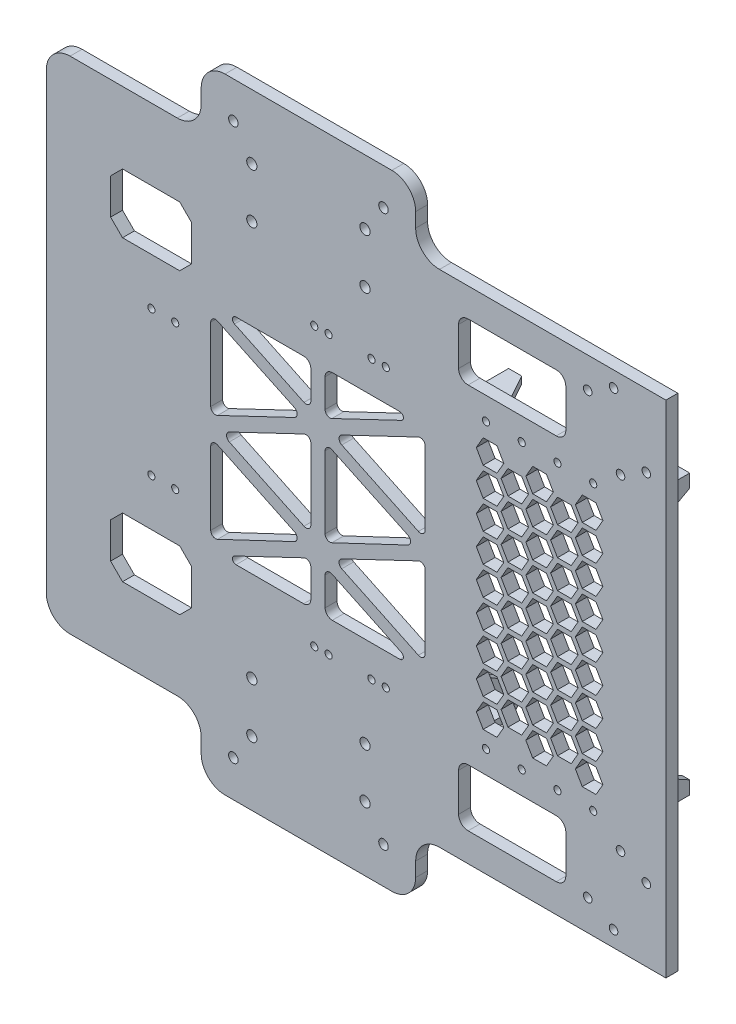
SolidWorks part; units mm, degrees
ref_plane "前视基准面" through (0, 0, 0) normal (0, 0, 1) x (1, 0, 0)
ref_plane "上视基准面" through (0, 0, 0) normal (0, 1, 0) x (1, 0, 0)
ref_plane "右视基准面" through (0, 0, 0) normal (1, 0, 0) x (0, 0, -1)
sketch "草图1" plane through (0, 0, 0) normal (0, 0, 1) x (1, 0, 0)
  line L2 (-130, 95) -> (-130, -95)
  line L3 (-120, -105) -> (-75, -105)
  line L4 (130, 95) -> (130, -95)
  line L5 (126.7518, 102.3765) -> (130, 105) construction
  line L6 (-130, -105) -> (-126.7518, -102.3765) construction
  line L9 (-65, -115) -> (-65, -121)
  line L10 (-55, -131) -> (15, -131)
  line L11 (25, -121) -> (25, -115)
  line L13 (35, -105) -> (120, -105)
  line L14 (126.7518, -102.3765) -> (130, -105) construction
  line L15 (-130, 105) -> (-126.7518, 102.3765) construction
  line L16 (-130, 0) -> (130, 0) construction
  line L17 (35, 105) -> (120, 105)
  line L18 (25, 121) -> (25, 115)
  line L19 (-55, 131) -> (15, 131)
  line L20 (-65, 115) -> (-65, 121)
  line L21 (-120, 105) -> (-75, 105)
  arc A1 (-120, -105) -> (-130, -95) centre (-120, -95) cw
  arc A3 (120, -105) -> (130, -95) centre (120, -95) ccw
  arc A8 (-65, -115) -> (-75, -105) centre (-75, -115) ccw
  arc A9 (25, -115) -> (35, -105) centre (35, -115) cw
  arc A10 (-55, -131) -> (-65, -121) centre (-55, -121) cw
  arc A11 (15, -131) -> (25, -121) centre (15, -121) ccw
  arc A12 (15, 131) -> (25, 121) centre (15, 121) cw
  arc A13 (-55, 131) -> (-65, 121) centre (-55, 121) ccw
  arc A14 (25, 115) -> (35, 105) centre (35, 115) ccw
  arc A15 (-65, 115) -> (-75, 105) centre (-75, 115) cw
  arc A16 (120, 105) -> (130, 95) centre (120, 95) cw
  arc A17 (-120, 105) -> (-130, 95) centre (-120, 95) ccw
  point P0 (0, 0)
  point P40 (25, -105)
  point P45 (25, 105)
  dimension "D2" = 10
  dimension "D3" = 65
  dimension "D4" = 10
  dimension "D5" = 105
  dimension "D7" = 10
  dimension "D8" = 10
  dimension "D10" = 10
  dimension "D12" = 10
  dimension "D13" = 105
  dimension "D18" = 90
  dimension "D19" = 6
extrude "凸台-拉伸1" add sketch "草图1" along normal blind 5
sketch "草图4" plane through (0, 0, 0) normal (0, 0, -1) x (-1, 0, 0)
  line L0 (-39, -47.5) -> (-39, -58.5)
  line L1 (-39, -58.5) -> (-50, -58.5)
  line L2 (-50, -58.5) -> (-50, -55.5)
  line L3 (-50, -55.5) -> (-42, -55.5)
  line L4 (-42, -55.5) -> (-42, -47.5)
  line L5 (-42, -47.5) -> (-39, -47.5)
  line L6 (-130, 0) -> (-25.5592, 0) construction
  line L7 (-130, -95) -> (-130, 95) construction
  line L10 (-130, -95) -> (-130, 95) construction
  dimension "D1" = 11
  dimension "D2" = 11
  dimension "D3" = 3
  dimension "D4" = 3
  dimension "D5" = 80
  dimension "D7" = 55.5
extrude "凸台-拉伸2" add sketch "草图4" along normal blind 20
sketch "草图5" plane through (0, -58.5, 0) normal (0, -1, 0) x (1, 0, 0)
  line L0 (50, -10) -> (44.5, -20)
  line L1 (50, -20) -> (50, 0) construction
  line L2 (50, -20) -> (39, -20) construction
  line L3 (44.5, -20) -> (50, -20)
  line L4 (50, -20) -> (50, -10)
  dimension "D1" = 10
  dimension "D2" = 5.5
extrude "切除-拉伸3" cut sketch "草图5" against normal blind 10
sketch "草图6" plane through (39, 0, 0) normal (-1, 0, 0) x (0, 0, 1)
  line L0 (-20, -53) -> (-10, -47.5)
  line L1 (-20, -58.5) -> (-20, -47.5) construction
  line L2 (-20, -47.5) -> (0, -47.5) construction
  line L3 (-10, -47.5) -> (-20, -47.5)
  line L4 (-20, -47.5) -> (-20, -53)
  dimension "D1" = 10
  dimension "D2" = 5.5
extrude "切除-拉伸4" cut sketch "草图6" against normal blind 10
ref_plane "基准面2" through (77, 0, 0) normal (1, 0, 0) x (0, 0, -1)
mirror "镜向1" about plane through (77, 0, 0) normal (1, 0, 0) of "凸台-拉伸2", "切除-拉伸4", "切除-拉伸3"
mirror "镜向2" about plane through (0, 0, 0) normal (0, 1, 0) of "镜向1"
sketch "草图7" plane through (0, 0, 0) normal (0, 0, -1) x (-1, 0, 0)
  line L4 (-112, -55.5) -> (-104, -55.5) construction
  line L5 (-112, 47.5) -> (-112, 55.5) construction
  line L6 (-112, 55.5) -> (-104, 55.5) construction
  line L7 (-92.013, 36) -> (-94.8997, 41)
  line L8 (-94.8997, 41) -> (-100.6732, 41)
  line L9 (-100.6732, 41) -> (-103.56, 36)
  line L10 (-103.56, 36) -> (-100.6732, 31)
  line L11 (-100.6732, 31) -> (-94.8997, 31)
  line L12 (-94.8997, 31) -> (-92.013, 36)
  line L13 (-77.0019, 36) -> (-97.7865, 36) construction
  line L14 (-74.1151, 31) -> (-71.2284, 36)
  line L15 (-71.2284, 36) -> (-74.1151, 41)
  line L16 (-74.1151, 41) -> (-79.8886, 41)
  line L17 (-79.8886, 41) -> (-82.7754, 36)
  line L18 (-82.7754, 36) -> (-79.8886, 31)
  line L19 (-79.8886, 31) -> (-74.1151, 31)
  line L20 (-92.013, 24) -> (-94.8997, 29)
  line L21 (-93.1677, 30) -> (-90.2809, 25)
  line L22 (-90.2809, 25) -> (-84.5074, 25)
  line L23 (-84.5074, 25) -> (-81.6207, 30)
  line L24 (-81.6207, 30) -> (-84.5074, 35)
  line L25 (-84.5074, 35) -> (-90.2809, 35)
  line L26 (-90.2809, 35) -> (-93.1677, 30)
  line L27 (-84.5074, 37) -> (-81.6207, 42)
  line L28 (-81.6207, 42) -> (-84.5074, 47)
  line L29 (-84.5074, 47) -> (-90.2809, 47)
  line L30 (-90.2809, 47) -> (-93.1677, 42)
  line L31 (-93.1677, 42) -> (-90.2809, 37)
  line L32 (-90.2809, 37) -> (-84.5074, 37)
  line L33 (-79.8886, 43) -> (-74.1151, 43)
  line L34 (-74.1151, 43) -> (-71.2284, 48)
  line L35 (-71.2284, 48) -> (-74.1151, 53)
  line L36 (-74.1151, 53) -> (-79.8886, 53)
  line L37 (-79.8886, 53) -> (-82.7754, 48)
  line L38 (-82.7754, 48) -> (-79.8886, 43)
  line L39 (-94.8997, 43) -> (-92.013, 48)
  line L40 (-92.013, 48) -> (-94.8997, 53)
  line L41 (-94.8997, 53) -> (-100.6732, 53)
  line L42 (-100.6732, 53) -> (-103.56, 48)
  line L43 (-103.56, 48) -> (-100.6732, 43)
  line L44 (-100.6732, 43) -> (-94.8997, 43)
  line L45 (-72.3831, 42) -> (-69.4963, 37)
  line L46 (-69.4963, 37) -> (-63.7228, 37)
  line L47 (-63.7228, 37) -> (-60.8361, 42)
  line L48 (-60.8361, 42) -> (-63.7228, 47)
  line L49 (-63.7228, 47) -> (-69.4963, 47)
  line L50 (-69.4963, 47) -> (-72.3831, 42)
  line L51 (-94.8997, 29) -> (-100.6732, 29)
  line L52 (-100.6732, 29) -> (-103.56, 24)
  line L53 (-103.56, 24) -> (-100.6732, 19)
  line L54 (-100.6732, 19) -> (-94.8997, 19)
  line L55 (-94.8997, 19) -> (-92.013, 24)
  line L56 (-93.1677, 18) -> (-90.2809, 13)
  line L57 (-90.2809, 13) -> (-84.5074, 13)
  line L58 (-84.5074, 13) -> (-81.6207, 18)
  line L59 (-81.6207, 18) -> (-84.5074, 23)
  line L60 (-84.5074, 23) -> (-90.2809, 23)
  line L61 (-90.2809, 23) -> (-93.1677, 18)
  line L62 (-74.1151, 19) -> (-71.2284, 24)
  line L63 (-71.2284, 24) -> (-74.1151, 29)
  line L64 (-74.1151, 29) -> (-79.8886, 29)
  line L65 (-79.8886, 29) -> (-82.7754, 24)
  line L66 (-82.7754, 24) -> (-79.8886, 19)
  line L67 (-79.8886, 19) -> (-74.1151, 19)
  line L68 (-72.3831, 30) -> (-69.4963, 25)
  line L69 (-69.4963, 25) -> (-63.7228, 25)
  line L70 (-63.7228, 25) -> (-60.8361, 30)
  line L71 (-60.8361, 30) -> (-63.7228, 35)
  line L72 (-63.7228, 35) -> (-69.4963, 35)
  line L73 (-69.4963, 35) -> (-72.3831, 30)
  line L74 (-92.013, 12) -> (-94.8997, 17)
  line L75 (-94.8997, 17) -> (-100.6732, 17)
  line L76 (-100.6732, 17) -> (-103.56, 12)
  line L77 (-103.56, 12) -> (-100.6732, 7)
  line L78 (-100.6732, 7) -> (-94.8997, 7)
  line L79 (-94.8997, 7) -> (-92.013, 12)
  line L80 (-93.1677, 6) -> (-90.2809, 1)
  line L81 (-90.2809, 1) -> (-84.5074, 1)
  line L82 (-84.5074, 1) -> (-81.6207, 6)
  line L83 (-81.6207, 6) -> (-84.5074, 11)
  line L84 (-84.5074, 11) -> (-90.2809, 11)
  line L85 (-90.2809, 11) -> (-93.1677, 6)
  line L86 (-74.1151, 7) -> (-71.2284, 12)
  line L87 (-71.2284, 12) -> (-74.1151, 17)
  line L88 (-74.1151, 17) -> (-79.8886, 17)
  line L89 (-79.8886, 17) -> (-82.7754, 12)
  line L90 (-82.7754, 12) -> (-79.8886, 7)
  line L91 (-79.8886, 7) -> (-74.1151, 7)
  line L92 (-72.3831, 18) -> (-69.4963, 13)
  line L93 (-69.4963, 13) -> (-63.7228, 13)
  line L94 (-63.7228, 13) -> (-60.8361, 18)
  line L95 (-60.8361, 18) -> (-63.7228, 23)
  line L96 (-63.7228, 23) -> (-69.4963, 23)
  line L97 (-69.4963, 23) -> (-72.3831, 18)
  line L98 (-92.013, 0) -> (-94.8997, 5)
  line L99 (-94.8997, 5) -> (-100.6732, 5)
  line L100 (-100.6732, 5) -> (-103.56, 0)
  line L101 (-103.56, 0) -> (-100.6732, -5)
  line L102 (-100.6732, -5) -> (-94.8997, -5)
  line L103 (-94.8997, -5) -> (-92.013, 0)
  line L104 (-93.1677, -6) -> (-90.2809, -11)
  line L105 (-90.2809, -11) -> (-84.5074, -11)
  line L106 (-84.5074, -11) -> (-81.6207, -6)
  line L107 (-81.6207, -6) -> (-84.5074, -1)
  line L108 (-84.5074, -1) -> (-90.2809, -1)
  line L109 (-90.2809, -1) -> (-93.1677, -6)
  line L110 (-74.1151, -5) -> (-71.2284, 0)
  line L111 (-71.2284, 0) -> (-74.1151, 5)
  line L112 (-74.1151, 5) -> (-79.8886, 5)
  line L113 (-79.8886, 5) -> (-82.7754, 0)
  line L114 (-82.7754, 0) -> (-79.8886, -5)
  line L115 (-79.8886, -5) -> (-74.1151, -5)
  line L116 (-72.3831, 6) -> (-69.4963, 1)
  line L117 (-69.4963, 1) -> (-63.7228, 1)
  line L118 (-63.7228, 1) -> (-60.8361, 6)
  line L119 (-60.8361, 6) -> (-63.7228, 11)
  line L120 (-63.7228, 11) -> (-69.4963, 11)
  line L121 (-69.4963, 11) -> (-72.3831, 6)
  line L122 (-92.013, -12) -> (-94.8997, -7)
  line L123 (-94.8997, -7) -> (-100.6732, -7)
  line L124 (-100.6732, -7) -> (-103.56, -12)
  line L125 (-103.56, -12) -> (-100.6732, -17)
  line L126 (-100.6732, -17) -> (-94.8997, -17)
  line L127 (-94.8997, -17) -> (-92.013, -12)
  line L128 (-93.1677, -18) -> (-90.2809, -23)
  line L129 (-90.2809, -23) -> (-84.5074, -23)
  line L130 (-84.5074, -23) -> (-81.6207, -18)
  line L131 (-81.6207, -18) -> (-84.5074, -13)
  line L132 (-84.5074, -13) -> (-90.2809, -13)
  line L133 (-90.2809, -13) -> (-93.1677, -18)
  line L134 (-74.1151, -17) -> (-71.2284, -12)
  line L135 (-71.2284, -12) -> (-74.1151, -7)
  line L136 (-74.1151, -7) -> (-79.8886, -7)
  line L137 (-79.8886, -7) -> (-82.7754, -12)
  line L138 (-82.7754, -12) -> (-79.8886, -17)
  line L139 (-79.8886, -17) -> (-74.1151, -17)
  line L140 (-72.3831, -6) -> (-69.4963, -11)
  line L141 (-69.4963, -11) -> (-63.7228, -11)
  line L142 (-63.7228, -11) -> (-60.8361, -6)
  line L143 (-60.8361, -6) -> (-63.7228, -1)
  line L144 (-63.7228, -1) -> (-69.4963, -1)
  line L145 (-69.4963, -1) -> (-72.3831, -6)
  line L146 (-92.013, -24) -> (-94.8997, -19)
  line L147 (-94.8997, -19) -> (-100.6732, -19)
  line L148 (-100.6732, -19) -> (-103.56, -24)
  line L149 (-103.56, -24) -> (-100.6732, -29)
  line L150 (-100.6732, -29) -> (-94.8997, -29)
  line L151 (-94.8997, -29) -> (-92.013, -24)
  line L152 (-93.1677, -30) -> (-90.2809, -35)
  line L153 (-90.2809, -35) -> (-84.5074, -35)
  line L154 (-84.5074, -35) -> (-81.6207, -30)
  line L155 (-81.6207, -30) -> (-84.5074, -25)
  line L156 (-84.5074, -25) -> (-90.2809, -25)
  line L157 (-90.2809, -25) -> (-93.1677, -30)
  line L158 (-74.1151, -29) -> (-71.2284, -24)
  line L159 (-71.2284, -24) -> (-74.1151, -19)
  line L160 (-74.1151, -19) -> (-79.8886, -19)
  line L161 (-79.8886, -19) -> (-82.7754, -24)
  line L162 (-82.7754, -24) -> (-79.8886, -29)
  line L163 (-79.8886, -29) -> (-74.1151, -29)
  line L164 (-72.3831, -18) -> (-69.4963, -23)
  line L165 (-69.4963, -23) -> (-63.7228, -23)
  line L166 (-63.7228, -23) -> (-60.8361, -18)
  line L167 (-60.8361, -18) -> (-63.7228, -13)
  line L168 (-63.7228, -13) -> (-69.4963, -13)
  line L169 (-69.4963, -13) -> (-72.3831, -18)
  line L170 (-92.013, -36) -> (-94.8997, -31)
  line L171 (-94.8997, -31) -> (-100.6732, -31)
  line L172 (-100.6732, -31) -> (-103.56, -36)
  line L173 (-103.56, -36) -> (-100.6732, -41)
  line L174 (-100.6732, -41) -> (-94.8997, -41)
  line L175 (-94.8997, -41) -> (-92.013, -36)
  line L176 (-93.1677, -42) -> (-90.2809, -47)
  line L177 (-90.2809, -47) -> (-84.5074, -47)
  line L178 (-84.5074, -47) -> (-81.6207, -42)
  line L179 (-81.6207, -42) -> (-84.5074, -37)
  line L180 (-84.5074, -37) -> (-90.2809, -37)
  line L181 (-90.2809, -37) -> (-93.1677, -42)
  line L182 (-74.1151, -41) -> (-71.2284, -36)
  line L183 (-71.2284, -36) -> (-74.1151, -31)
  line L184 (-74.1151, -31) -> (-79.8886, -31)
  line L185 (-79.8886, -31) -> (-82.7754, -36)
  line L186 (-82.7754, -36) -> (-79.8886, -41)
  line L187 (-79.8886, -41) -> (-74.1151, -41)
  line L188 (-72.3831, -30) -> (-69.4963, -35)
  line L189 (-69.4963, -35) -> (-63.7228, -35)
  line L190 (-63.7228, -35) -> (-60.8361, -30)
  line L191 (-60.8361, -30) -> (-63.7228, -25)
  line L192 (-63.7228, -25) -> (-69.4963, -25)
  line L193 (-69.4963, -25) -> (-72.3831, -30)
  line L194 (-92.013, -48) -> (-94.8997, -43)
  line L195 (-94.8997, -43) -> (-100.6732, -43)
  line L196 (-100.6732, -43) -> (-103.56, -48)
  line L197 (-103.56, -48) -> (-100.6732, -53)
  line L198 (-100.6732, -53) -> (-94.8997, -53)
  line L199 (-94.8997, -53) -> (-92.013, -48)
  line L206 (-74.1151, -53) -> (-71.2284, -48)
  line L207 (-71.2284, -48) -> (-74.1151, -43)
  line L208 (-74.1151, -43) -> (-79.8886, -43)
  line L209 (-79.8886, -43) -> (-82.7754, -48)
  line L210 (-82.7754, -48) -> (-79.8886, -53)
  line L211 (-79.8886, -53) -> (-74.1151, -53)
  line L212 (-72.3831, -42) -> (-69.4963, -47)
  line L213 (-69.4963, -47) -> (-63.7228, -47)
  line L214 (-63.7228, -47) -> (-60.8361, -42)
  line L215 (-60.8361, -42) -> (-63.7228, -37)
  line L216 (-63.7228, -37) -> (-69.4963, -37)
  line L217 (-69.4963, -37) -> (-72.3831, -42)
  line L218 (-61.9908, 36) -> (-59.104, 31)
  line L219 (-61.9908, 48) -> (-59.104, 43)
  line L220 (-59.104, 43) -> (-53.3305, 43)
  line L221 (-53.3305, 43) -> (-50.4438, 48)
  line L222 (-50.4438, 48) -> (-53.3305, 53)
  line L223 (-53.3305, 53) -> (-59.104, 53)
  line L224 (-59.104, 53) -> (-61.9908, 48)
  line L225 (-59.104, 31) -> (-53.3305, 31)
  line L226 (-53.3305, 31) -> (-50.4438, 36)
  line L227 (-50.4438, 36) -> (-53.3305, 41)
  line L228 (-53.3305, 41) -> (-59.104, 41)
  line L229 (-59.104, 41) -> (-61.9908, 36)
  line L230 (-61.9908, 24) -> (-59.104, 19)
  line L231 (-59.104, 19) -> (-53.3305, 19)
  line L232 (-53.3305, 19) -> (-50.4438, 24)
  line L233 (-50.4438, 24) -> (-53.3305, 29)
  line L234 (-53.3305, 29) -> (-59.104, 29)
  line L235 (-59.104, 29) -> (-61.9908, 24)
  line L236 (-61.9908, 12) -> (-59.104, 7)
  line L237 (-59.104, 7) -> (-53.3305, 7)
  line L238 (-53.3305, 7) -> (-50.4438, 12)
  line L239 (-50.4438, 12) -> (-53.3305, 17)
  line L240 (-53.3305, 17) -> (-59.104, 17)
  line L241 (-59.104, 17) -> (-61.9908, 12)
  line L242 (-61.9908, 0) -> (-59.104, -5)
  line L243 (-59.104, -5) -> (-53.3305, -5)
  line L244 (-53.3305, -5) -> (-50.4438, 0)
  line L245 (-50.4438, 0) -> (-53.3305, 5)
  line L246 (-53.3305, 5) -> (-59.104, 5)
  line L247 (-59.104, 5) -> (-61.9908, 0)
  line L248 (-61.9908, -12) -> (-59.104, -17)
  line L249 (-59.104, -17) -> (-53.3305, -17)
  line L250 (-53.3305, -17) -> (-50.4438, -12)
  line L251 (-50.4438, -12) -> (-53.3305, -7)
  line L252 (-53.3305, -7) -> (-59.104, -7)
  line L253 (-59.104, -7) -> (-61.9908, -12)
  line L254 (-61.9908, -24) -> (-59.104, -29)
  line L255 (-59.104, -29) -> (-53.3305, -29)
  line L256 (-53.3305, -29) -> (-50.4438, -24)
  line L257 (-50.4438, -24) -> (-53.3305, -19)
  line L258 (-53.3305, -19) -> (-59.104, -19)
  line L259 (-59.104, -19) -> (-61.9908, -24)
  line L260 (-61.9908, -36) -> (-59.104, -41)
  line L261 (-59.104, -41) -> (-53.3305, -41)
  line L262 (-53.3305, -41) -> (-50.4438, -36)
  line L263 (-50.4438, -36) -> (-53.3305, -31)
  line L264 (-53.3305, -31) -> (-59.104, -31)
  line L265 (-59.104, -31) -> (-61.9908, -36)
  line L266 (-61.9908, -48) -> (-59.104, -53)
  line L267 (-59.104, -53) -> (-53.3305, -53)
  line L268 (-53.3305, -53) -> (-50.4438, -48)
  line L269 (-50.4438, -48) -> (-53.3305, -43)
  line L270 (-53.3305, -43) -> (-59.104, -43)
  line L271 (-59.104, -43) -> (-61.9908, -48)
  line L272 (-93.1677, -54) -> (-90.2809, -59) [skipped]
  line L273 (-90.2809, -59) -> (-84.5074, -59) [skipped]
  line L274 (-84.5074, -59) -> (-81.6207, -54) [skipped]
  line L275 (-81.6207, -54) -> (-84.5074, -49) [skipped]
  line L276 (-84.5074, -49) -> (-90.2809, -49) [skipped]
  line L277 (-90.2809, -49) -> (-93.1677, -54) [skipped]
  circle A0 centre (-97.7865, 36) radius 5 construction
  circle A1 centre (-77.0019, 36) radius 5 construction
  circle A2 centre (-87.3942, 30) radius 5 construction
  circle A3 centre (-87.3942, 42) radius 5 construction
  circle A4 centre (-77.0019, 48) radius 5 construction
  circle A5 centre (-97.7865, 48) radius 5 construction
  circle A6 centre (-66.6096, 42) radius 5 construction
  circle A7 centre (-56.2173, 48) radius 5 construction
  point P4 (-87.3942, 37)
  dimension "D1" = 2
  dimension "D3" = 10
  dimension "D4" = 10
  dimension "D5" = 2
  dimension "D7" = 10
  dimension "D11" = 10
  dimension "D14" = 10
  dimension "D15" = 10
  dimension "D20" = 10
  dimension "D2" = 2
  dimension "D6" = 2
  dimension "D8" = 2
  dimension "D9" = 2
  dimension "D10" = 2
  dimension "D12" = 2
  dimension "D13" = 2
  dimension "D16" = 2
  dimension "D17" = 2
  dimension "D19" = 2
  dimension "D21" = 9
  dimension "D22" = 2.5
  dimension "D23" = 2.5
  dimension "D24" = 8.44
  dimension "D18" = 8
extrude "切除-拉伸5" cut sketch "草图7" against normal blind 5
sketch "草图8" plane through (0, 0, 0) normal (0, 0, -1) x (-1, 0, 0)
  line L0 (-75.3677, 120) -> (-75.3677, -120)
  line L1 (-100.0285, 77.2863) -> (-100.0285, -77.2863)
  line L2 (-100.0285, 77.2863) -> (-75.3677, 120)
  line L3 (-100.0285, -77.2863) -> (-75.3677, -120)
  line L4 (-37.1297, 0) -> (-146.8562, 0) construction
  dimension "D1" = 30
  dimension "D2" = 30
  dimension "D3" = 120
  dimension "D4" = 120
sketch "草图9" plane through (0, 0, 0) normal (0, 0, -1) x (-1, 0, 0)
  line L0 (148.8518, 0) -> (-37.1297, 0) construction
  line L1 (-29, 41) -> (-29, 4)
  line L2 (-25, -45) -> (13, -45)
  line L3 (61, -41) -> (61, -4)
  line L4 (57, 45) -> (19, 45)
  line L14 (-29, 41) -> (9.8049, 22.5)
  line L15 (57, 0) -> (19, -18.1163)
  line L16 (130, 95) -> (130, -95) construction
  line L17 (63, 93) -> (118, 93)
  line L18 (63, 93) -> (63, 66)
  line L19 (63, 66) -> (118, 66)
  line L20 (118, 93) -> (118, 66)
  line L21 (75, 105) -> (120, 105) construction
  line L22 (63, -66) -> (118, -66)
  line L23 (118, -93) -> (118, -66)
  line L24 (63, -93) -> (118, -93)
  line L25 (63, -93) -> (63, -66)
  line L26 (-120, 105) -> (-35, 105) construction
  line L27 (-43, 93) -> (-88, 93)
  line L28 (-43, 93) -> (-43, 69)
  line L29 (-43, 69) -> (-88, 69)
  line L30 (-88, 93) -> (-88, 69)
  line L31 (-130, -95) -> (-130, 95) construction
  line L32 (-43, -69) -> (-88, -69)
  line L33 (-88, -93) -> (-88, -69)
  line L34 (-43, -93) -> (-88, -93)
  line L35 (-43, -93) -> (-43, -69)
  line L36 (-25, 45) -> (13, 26.8837)
  line L37 (-25, -45) -> (13, -26.8837)
  line L38 (61, 41) -> (22.0746, 22.5575)
  line L39 (-25.5359, 0) -> (13, -18.258)
  line L40 (57, 45) -> (19, 26.8837)
  line L41 (57, -45) -> (19, -26.8837)
  line L42 (16, 61.4977) -> (16, -60.5731) construction
  line L43 (13, 45) -> (13, 26.8837)
  line L44 (19, 45) -> (19, 26.8837)
  line L45 (13, 18.258) -> (13, -18.258)
  line L46 (9.8049, 22.5) -> (-29, 4)
  line L47 (19, 18.1163) -> (57, 0)
  line L48 (22.0746, 22.5575) -> (61, 4)
  line L49 (13, 18.258) -> (-25.5359, 0)
  line L50 (19, 18.1163) -> (19, -18.1163)
  line L51 (22.0746, -22.5575) -> (61, -41)
  line L52 (9.8049, -22.5) -> (-29, -41)
  line L53 (9.8049, -22.5) -> (-29, -4)
  line L54 (22.0746, -22.5575) -> (61, -4)
  line L55 (13, -26.8837) -> (13, -45)
  line L56 (19, -26.8837) -> (19, -45)
  line L57 (13, 45) -> (-25, 45)
  line L58 (-29, -4) -> (-29, -41)
  line L59 (19, -45) -> (57, -45)
  line L60 (61, 4) -> (61, 41)
  line L61 (-44, 41) -> (-44, -37.8122) construction
  dimension "D1" = 45
  dimension "D2" = 45
  dimension "D3" = 15
  dimension "D4" = 90
  dimension "D5" = 1
  dimension "D7" = 12
  dimension "D8" = 12
  dimension "D9" = 27
  dimension "D10" = 55
  dimension "D11" = 12
  dimension "D12" = 45
  dimension "D13" = 42
  dimension "D14" = 24
  dimension "D21" = 4
  dimension "D22" = 4
  dimension "D23" = 4
  dimension "D24" = 4
  dimension "D26" = 4
  dimension "D27" = 3
  dimension "D28" = 45
extrude "切除-拉伸6" cut sketch "草图9" against normal blind 5 contours L27 L30 L29 L28 | L34 L35 L32 L33 | L4 L44 L40 | L48 L60 L38 | L47 L50 L15 | L54 L51 L3 | L56 L59 L41 | L55 L37 L2 | L53 L58 L52 | L45 L49 L39 | L46 L14 L1 | L43 L57 L36 | L57 L36 L43 region at (16.065, 22.5, 0) region at (-0.3333, -38.9612, 0) region at (-48.0249, -22.5192, 0) region at (-31.6667, 38.9612, 0) region at (-31.6667, 0, 0) region at (65.5, 81, 0) region at (65.5, -81, 0) region at (-0.3333, 38.9612, 0) region at (-48.0249, 22.5192, 0) region at (-0.1547, 0, 0) region at (-31.6667, -38.9612, 0) region at (16.065, -22.5, 0)
fillet "圆角1" radius 4 8 edges at (43, -93, 2.5) (88, -69, 2.5) (43, -69, 2.5) (88, -93, 2.5) (88, 69, 2.5) (43, 69, 2.5) (43, 93, 2.5) (88, 93, 2.5)
fillet "圆角2" radius 1.5 4 edges at (25, -45, 2.5) (-57, -45, 2.5) (25, 45, 2.5) (-57, 45, 2.5)
fillet "圆角3" radius 2 22 edges at (29, -4, 2.5) (29, 4, 2.5) (-13, -18.258, 2.5) (-61, -41, 2.5) (-61, 4, 2.5) (-13, -26.8837, 2.5) (-13, 18.258, 2.5) (-61, -4, 2.5) (-22.0746, -22.5575, 2.5) (25.5359, 0, 2.5) (-22.0746, 22.5575, 2.5) (-61, 41, 2.5) (-19, 26.8837, 2.5) (-19, -26.8837, 2.5) (-19, -18.1163, 2.5) (29, -41, 2.5) (29, 41, 2.5) (-57, 0, 2.5) (-9.8049, -22.5, 2.5) (-13, 26.8837, 2.5) (-9.8049, 22.5, 2.5) (-19, 18.1163, 2.5)
fillet "圆角4" radius 3 4 edges at (-13, -45, 2.5) (-13, 45, 2.5) (-19, -45, 2.5) (-19, 45, 2.5)
sketch "草图12" plane through (0, 0, 0) normal (0, 0, -1) x (-1, 0, 0)
  line L1 (-120, 105) -> (-130, 105)
  line L2 (-120, 105) -> (-120, -105)
  line L3 (-120, -105) -> (-130, -105)
  line L4 (-130, 105) -> (-130, -105)
extrude "凸台-拉伸3" add sketch "草图12" against normal up to surface (5 mm away) up to face at (65.5, 81, 5)
sketch "草图10" plane through (0, 0, 0) normal (0, 0, -1) x (-1, 0, 0)
  line L0 (-37.1297, 0) -> (-146.8562, 0) construction
  line L1 (-37.1297, 0) -> (-146.8562, 0) construction
  circle A0 centre (-121.782, 74.6081) radius 1.8 construction
  circle A1 centre (-110.9567, 68.3581) radius 1.8 construction
  circle A2 centre (-108.032, 98.4238) radius 1.8 construction
  circle A3 centre (-97.2067, 92.1738) radius 1.8 construction
  circle A4 centre (-3.75, 104) radius 2.15 construction
  circle A5 centre (-3.75, 104) radius 2.15
  circle A6 centre (-3.75, -104) radius 2.15
  circle A15 centre (-121.782, 74.6081) radius 1.8
  circle A16 centre (-110.9567, 68.3581) radius 1.8
  circle A17 centre (-108.032, 98.4238) radius 1.8
  circle A18 centre (-97.2067, 92.1738) radius 1.8
  circle A41 centre (-97.2067, -92.1738) radius 1.8
  circle A42 centre (-108.032, -98.4238) radius 1.8
  circle A43 centre (-110.9567, -68.3581) radius 1.8
  circle A44 centre (-121.782, -74.6081) radius 1.8
  circle A45 centre (-99.5, 59.5) radius 1.5 construction
  circle A46 centre (-84.5, 59.5) radius 1.5 construction
  circle A47 centre (-69.5, 59.5) radius 1.5 construction
  circle A48 centre (-54.5, 59.5) radius 1.5 construction
  circle A49 centre (-12.4571, 58.25) radius 1.5 construction
  circle A50 centre (-6.4571, 58.25) radius 1.5 construction
  circle A51 centre (11.5429, 58.25) radius 1.5 construction
  circle A52 centre (17.5429, 58.25) radius 1.5 construction
  circle A53 centre (-99.5, 59.5) radius 1.5
  circle A54 centre (-84.5, 59.5) radius 1.5
  circle A55 centre (-69.5, 59.5) radius 1.5
  circle A56 centre (-54.5, 59.5) radius 1.5
  circle A57 centre (-12.4571, 58.25) radius 1.5
  circle A58 centre (-6.4571, 58.25) radius 1.5
  circle A59 centre (11.5429, 58.25) radius 1.5
  circle A60 centre (17.5429, 58.25) radius 1.5
  circle A61 centre (17.5429, -58.25) radius 1.5
  circle A62 centre (11.5429, -58.25) radius 1.5
  circle A63 centre (-6.4571, -58.25) radius 1.5
  circle A64 centre (-12.4571, -58.25) radius 1.5
  circle A65 centre (-54.5, -59.5) radius 1.5
  circle A66 centre (-69.5, -59.5) radius 1.5
  circle A67 centre (-84.5, -59.5) radius 1.5
  circle A68 centre (-99.5, -59.5) radius 1.5
  circle A89 centre (75.897, 30.3) radius 1.5 construction
  circle A90 centre (85.897, 30.3) radius 1.5 construction
  circle A91 centre (75.897, 30.3) radius 1.5
  circle A92 centre (85.897, 30.3) radius 1.5
  circle A93 centre (85.897, -30.3) radius 1.5
  circle A94 centre (75.897, -30.3) radius 1.5
  circle A95 centre (43.75, 83) radius 2.15 construction
  circle A96 centre (43.75, 104) radius 2.15 construction
  circle A97 centre (-3.75, 83) radius 2.15 construction
  circle A99 centre (43.75, 83) radius 2.15
  circle A100 centre (43.75, 104) radius 2.15
  circle A101 centre (-3.75, 83) radius 2.15
  circle A104 centre (-3.75, -83) radius 2.15
  circle A105 centre (43.75, -104) radius 2.15
  circle A106 centre (43.75, -83) radius 2.15
extrude "切除-拉伸7" cut sketch "草图10" against normal through all
sketch "草图11" plane through (0, 0, 0) normal (0, 0, -1) x (-1, 0, 0)
  line L0 (130, 95) -> (130, -95) construction
  line L1 (74, -75) -> (98, -75)
  line L2 (69, -70) -> (69, -55)
  line L3 (74, -50) -> (98, -50)
  line L4 (103, -70) -> (103, -55)
  line L5 (130, 0) -> (108.529, 0) construction
  line L10 (69, -70) -> (74, -75)
  line L11 (69, -55) -> (74, -50)
  line L12 (98, -50) -> (103, -55)
  line L13 (98, -75) -> (103, -70)
  line L14 (98, 75) -> (103, 70)
  line L15 (98, 50) -> (103, 55)
  line L16 (69, 55) -> (74, 50)
  line L17 (69, 70) -> (74, 75)
  line L18 (103, 70) -> (103, 55)
  line L19 (74, 50) -> (98, 50)
  line L20 (69, 70) -> (69, 55)
  line L21 (74, 75) -> (98, 75)
  point P0 (69, -75)
  point P1 (103, -50)
  point P2 (69, -50)
  point P3 (103, -75)
  point P8 (103, 75)
  point P9 (69, 50)
  point P10 (103, 50)
  point P11 (69, 75)
  dimension "D1" = 34
  dimension "D2" = 25
  dimension "D3" = 27
  dimension "D4" = 50
extrude "切除-拉伸8" cut sketch "草图11" against normal through all
sketch "草图14" plane through (0, 0, 5) normal (0, 0, 1) x (1, 0, 0)
  line L0 (25, -121) -> (25, -115) construction
  line L1 (-55, -131) -> (15, -131) construction
  line L2 (-20, -131) -> (-20, 131) construction
  line L3 (15, 131) -> (-55, 131) construction
  line L4 (-20, 0) -> (-130, 0) construction
  line L5 (-130, 95) -> (-130, -95) construction
  circle A0 centre (11.5, -115.68) radius 2
  circle A1 centre (-51.5, -115.68) radius 2
  circle A2 centre (-51.5, 115.68) radius 2
  circle A3 centre (11.5, 115.68) radius 2
  dimension "D1" = 4
  dimension "D2" = 13.5
  dimension "D3" = 15.32
extrude "切除-拉伸9" cut sketch "草图14" against normal blind 10
equation "\"45、\"=43.7672"
